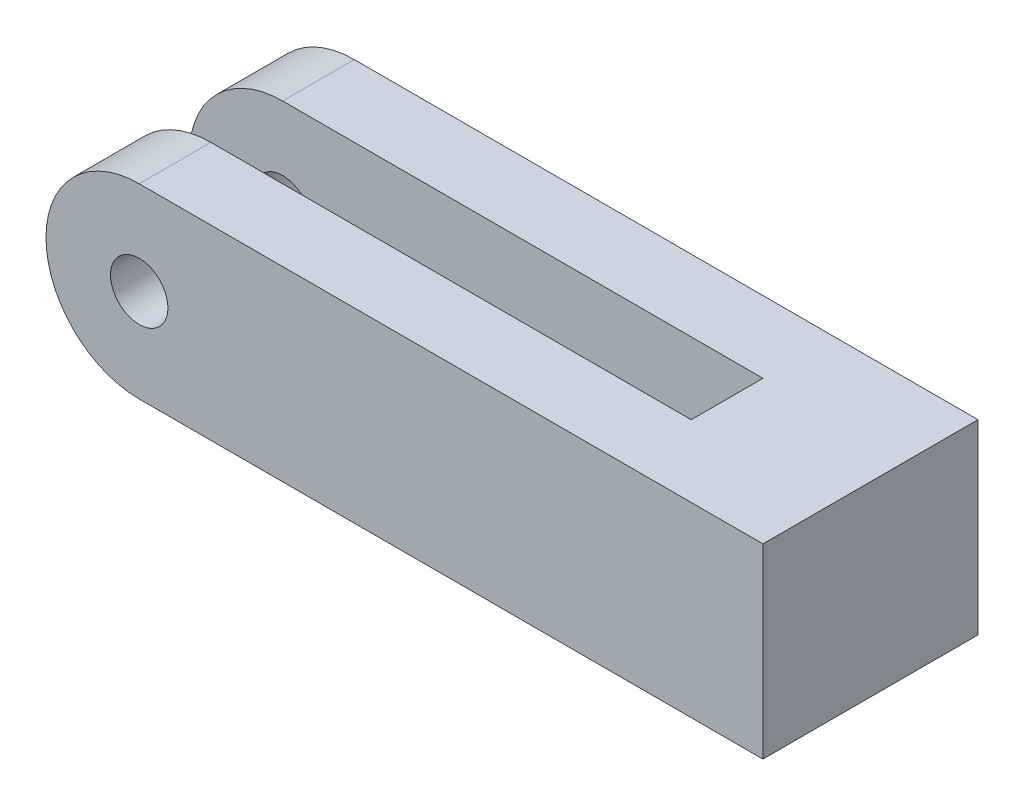
SolidWorks part; units mm, degrees
ref_plane "前视基准面" through (0, 0, 0) normal (0, 0, 1) x (1, 0, 0)
ref_plane "上视基准面" through (0, 0, 0) normal (0, 1, 0) x (1, 0, 0)
ref_plane "右视基准面" through (0, 0, 0) normal (1, 0, 0) x (0, 0, -1)
sketch "草图1" plane through (0, 0, 0) normal (0, 0, 1) x (1, 0, 0)
  line L1 (-60, -13) -> (60, -13)
  line L2 (-60, -13) -> (-60, 13)
  line L3 (-60, 13) -> (60, 13)
  line L4 (60, -13) -> (60, 13)
  line L5 (-60, -13) -> (60, 13) construction
  line L6 (-60, 13) -> (60, -13) construction
  point P0 (0, 0)
  dimension "D1" = 120
  dimension "D2" = 26
extrude "凸台-拉伸1" add sketch "草图1" along normal blind 15
sketch "草图5" plane through (0, 0, 0) normal (0, 0, -1) x (-1, 0, 0)
  line L3 (-60, 13) -> (60, 13) construction
  line L4 (60, -13) -> (-60, -13) construction
  arc A0 (27, -13) -> (27, 13) centre (27, 0) ccw
extrude "切除-拉伸8" cut sketch "草图5" against normal through all and the other way through all flip side to cut
sketch "草图6" plane through (0, 0, 0) normal (0, 0, -1) x (-1, 0, 0)
  line L2 (-40, 13) -> (-40, -13)
  line L3 (-60, 13) -> (27, 13) construction
  line L4 (27, -13) -> (-60, -13) construction
  line L5 (-60, -13) -> (-60, 13) construction
  dimension "D1" = 20
extrude "切除-拉伸9" cut sketch "草图6" against normal blind 5 and the other way through all
sketch "草图7" plane through (0, 0, 5) normal (0, 0, -1) x (-1, 0, 0)
  circle A0 centre (27, 0) radius 4
extrude "切除-拉伸10" cut sketch "草图7" against normal through all and the other way through all
mirror "镜向2" about plane through (0, 0, 0) normal (0, 0, -1) of bodies 113
